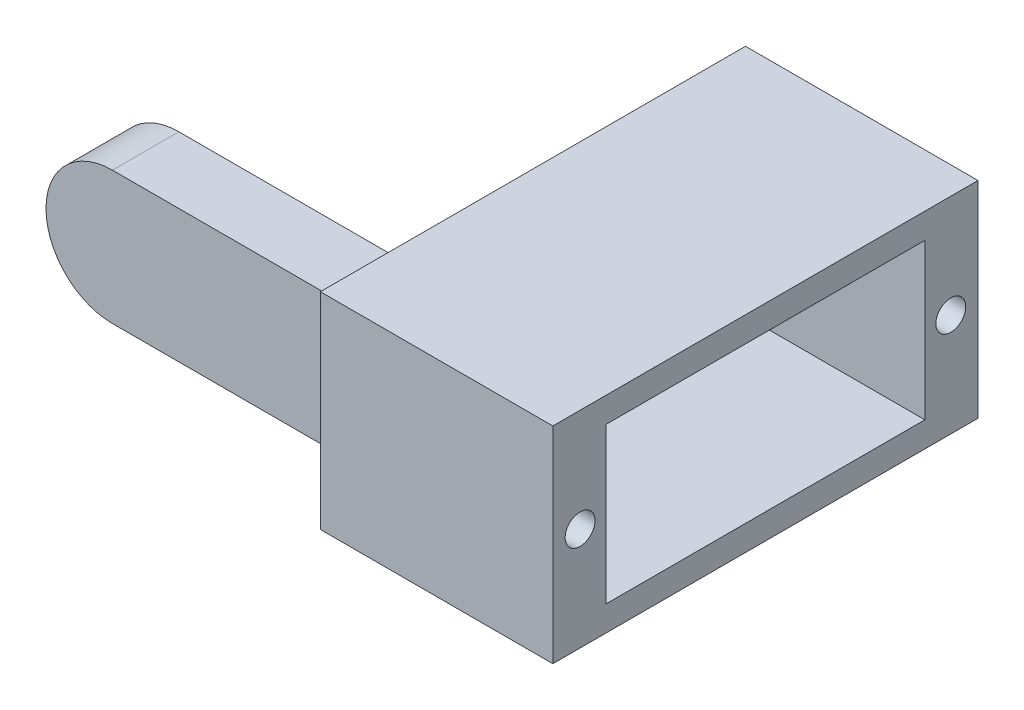
SolidWorks part; units mm, degrees
ref_plane "Front" through (0, 0, 0) normal (0, 0, 1) x (1, 0, 0)
ref_plane "Top" through (0, 0, 0) normal (0, 1, 0) x (1, 0, 0)
ref_plane "Right" through (0, 0, 0) normal (1, 0, 0) x (0, 0, -1)
sketch "Sketch1" plane through (0, 0, 0) normal (0, 0, 1) x (1, 0, 0)
  line L0 (0, 0) -> (20.9, 0) construction
  line L1 (0, 5) -> (20.9, 5)
  line L2 (0, -5) -> (20.9, -5)
  line L3 (20.9, -5) -> (20.9, 5)
  line L8 (21, -5.75) -> (36, -5.75)
  line L9 (36, -5.75) -> (36, 5.75)
  line L10 (36, 5.75) -> (21, 5.75)
  line L11 (21, 5.75) -> (21, -5.75)
  line L12 (21, -5.75) -> (36, -5.75) construction
  line L13 (36, -5.75) -> (36, 5.75) construction
  line L14 (36, 5.75) -> (21, 5.75) construction
  line L15 (21, 5.75) -> (21, -5.75) construction
  arc A0 (0, 5) -> (0, -5) centre (0, 0) ccw
  dimension "D1" = 0
  dimension "D2" = 10
  dimension "D3" = 0.1
extrude "Boss-Extrude1" add sketch "Sketch1" along normal blind 5 contours L1 L3 L2 A0
sketch "Sketch2" plane through (0, 0, 0) normal (0, 0, -1) x (-1, 0, 0)
  circle A0 centre (0, 0) radius 2.35
  dimension "D1" = 4.7
extrude "Cut-Extrude1" cut sketch "Sketch2" against normal blind 3 contours A0
ref_plane "Plane1" through (0, 0, -14.3) normal (0, 0, -1) x (-1, 0, 0)
ref_axis "Axis1" through (-6.295, 0, -14.3) along (1, 0, 0)
sketch "Sketch3" plane through (20.9, 0, 0) normal (1, 0, 0) x (0, 0, -1)
  line L0 (-7.85, 5.75) -> (-7.85, -5.75) construction
  line L1 (-7.85, 7.75) -> (-7.85, -7.75)
  line L2 (-7.85, 7.75) -> (24.15, 7.75)
  line L3 (-7.85, -7.75) -> (24.15, -7.75)
  line L4 (24.15, 5.75) -> (24.15, -5.75) construction
  line L5 (24.15, 7.75) -> (24.15, -7.75)
  line L6 (0, -5) -> (0, 5)
  line L7 (0, 5) -> (-5, 5)
  line L8 (-5, 5) -> (-5, -5)
  line L9 (-5, -5) -> (0, -5)
  line L10 (0, -5) -> (0, 5)
  line L11 (0, 5) -> (-5, 5)
  line L12 (-5, 5) -> (-5, -5)
  line L13 (-5, -5) -> (0, -5)
  line L15 (-3.75, -5.75) -> (20.05, -5.75) construction
  line L16 (-3.75, 5.75) -> (20.05, 5.75) construction
  line M5 (0, -5) -> (0, 5)
  line M6 (0, 5) -> (-5, 5)
  line M7 (-5, 5) -> (-5, -5)
  line M8 (-5, -5) -> (0, -5)
  dimension "D2" = 2
  dimension "D3" = 2
  dimension "D1" = 0
extrude "Boss-Extrude2" add sketch "Sketch3" against normal blind 2.4 contours L5 L2 L1 L3 M5 M8 M7 M6 region at (20.9, 0, -9.3439)
sketch "Sketch4" plane through (20.9, 0, 0) normal (1, 0, 0) x (0, 0, -1)
  line L8 (-3.85, 5.85) -> (-3.85, -5.85)
  line L9 (20.15, 5.85) -> (-3.85, 5.85)
  line L10 (20.15, -5.85) -> (20.15, 5.85)
  line L11 (-3.85, -5.85) -> (20.15, -5.85)
  line L12 (-3.85, 5.85) -> (-3.85, -5.85)
  line L13 (20.15, 5.85) -> (-3.85, 5.85)
  line L14 (20.15, -5.85) -> (20.15, 5.85)
  line L15 (-3.85, -5.85) -> (20.15, -5.85)
  line L16 (24.15, -7.75) -> (24.15, 7.75)
  line L17 (24.15, 7.75) -> (-7.85, 7.75)
  line L18 (-7.85, 7.75) -> (-7.85, -7.75)
  line L19 (-7.85, -7.75) -> (24.15, -7.75)
  line L20 (24.15, -7.75) -> (24.15, 7.75)
  line L21 (24.15, 7.75) -> (-7.85, 7.75)
  line L22 (-7.85, 7.75) -> (-7.85, -7.75)
  line L23 (-7.85, -7.75) -> (24.15, -7.75)
  dimension "D1" = 0.1
  dimension "D2" = 0
extrude "Boss-Extrude3" add sketch "Sketch4" along normal up to surface (15.1 mm away)
sketch "Sketch6" plane through (36, 0, 0) normal (1, 0, 0) x (0, 0, -1)
  circle A0 centre (-5.8, 0) radius 1.125 construction
  circle A1 centre (-5.8, 0) radius 1.125
  circle A2 centre (22.1, 0) radius 1.125 construction
  circle A3 centre (22.1, 0) radius 1.125
extrude "Cut-Extrude2" cut sketch "Sketch6" against normal blind 8
